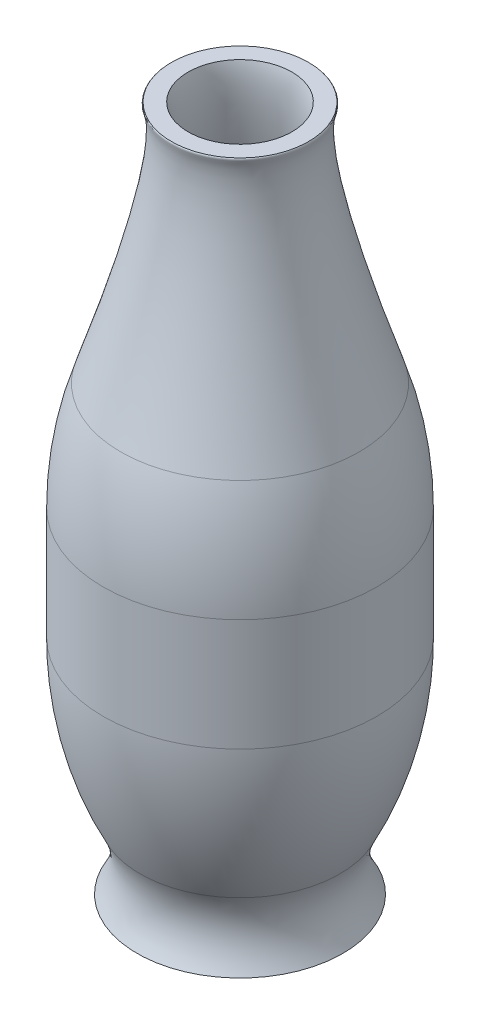
SolidWorks part; units mm, degrees
ref_plane "前视基准面" through (0, 0, 0) normal (0, 0, 1) x (1, 0, 0)
ref_plane "上视基准面" through (0, 0, 0) normal (0, 1, 0) x (1, 0, 0)
ref_plane "右视基准面" through (0, 0, 0) normal (1, 0, 0) x (0, 0, -1)
sketch "草图1" plane through (0, 0, 0) normal (0, 0, 1) x (1, 0, 0)
  line L0 (0, 0) -> (0, 20)
  line L1 (0, 20) -> (2, 20)
  line L2 (3.0003, 0) -> (0, 0)
  line L3 (3.9869, 9.7454) -> (3.9869, 6.4772)
  arc A0 (2.9095, 1.962) -> (3.9869, 6.4772) centre (-6.0131, 6.4772) ccw
  arc A1 (3.9869, 9.7454) -> (3.4762, 12.9003) centre (-6.0131, 9.7454) ccw
  spline S0 degree 3 poles (2, 20) (2.0749, 19.9227) (1.6746, 19.7971) (2.3378, 16.3245) (3.4762, 12.9003) knots 0 0 0 0 0.23005 0.4601 0.4601 0.4601 0.4601
  spline S1 degree 3 poles (2.9095, 1.962) (2.759, 1.6645) (2.575, 1.0615) (2.7709, 0.378) (3.0003, 0) knots 0.735355 0.735355 0.735355 0.735355 0.77188 0.808404 0.808404 0.808404 0.808404
revolve "旋转2" add sketch "草图1" angle 360 about L0
shell "抽壳2" thickness 0.5 removed face at (0, 20, -2)
scale "缩放比例1" scale about centroid uniform scaling yes scale factor 0.4
